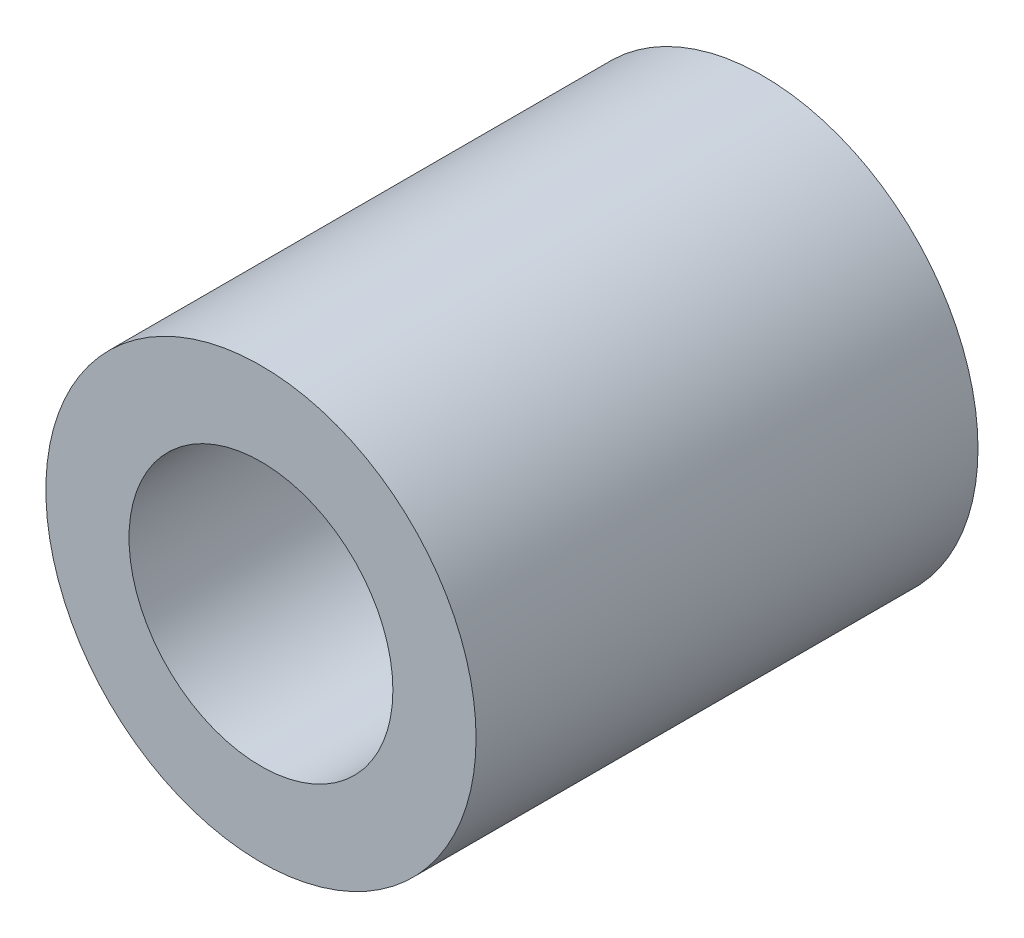
SolidWorks part; units mm, degrees
material "Nylon 6/10"
ref_plane "Front Plane" through (0, 0, 0) normal (0, 0, 1) x (1, 0, 0)
ref_plane "Top Plane" through (0, 0, 0) normal (0, 1, 0) x (1, 0, 0)
ref_plane "Right Plane" through (0, 0, 0) normal (1, 0, 0) x (0, 0, -1)
sketch "Sketch1" plane through (0, 0, 0) normal (0, 0, 1) x (1, 0, 0)
  circle A0 centre (0, 0) radius 2.3813
  circle A1 centre (0, 0) radius 1.4605
  dimension "OD" = 4.7625
  dimension "ID" = 2.921
extrude "Extrude1" add sketch "Sketch1" along normal mid plane 5.5562
sketch "Sketch2" plane through (0, 0, 0) normal (1, 0, 0) x (0, 0, -1)
  line L0 (-2.7781, -1.4605) -> (2.7781, -1.4605) construction
  line L3 (2.7781, 1.4605) -> (-2.7781, 1.4605) construction
  line L5 (-2.7781, -1.4605) -> (2.7781, -1.4605)
  line L6 (2.7781, 1.4605) -> (-2.7781, 1.4605)
sketch "Sketch4" plane through (0, 0, 2.7781) normal (0, 0, 1) x (1, 0, 0)
  line L0 (0, 0) -> (-1.0327, 1.0327)
  line L1 (0, -2.6194) -> (0, 2.6194) construction
  circle A0 centre (0, 0) radius 1.4605 construction
  dimension "D1" = 45
